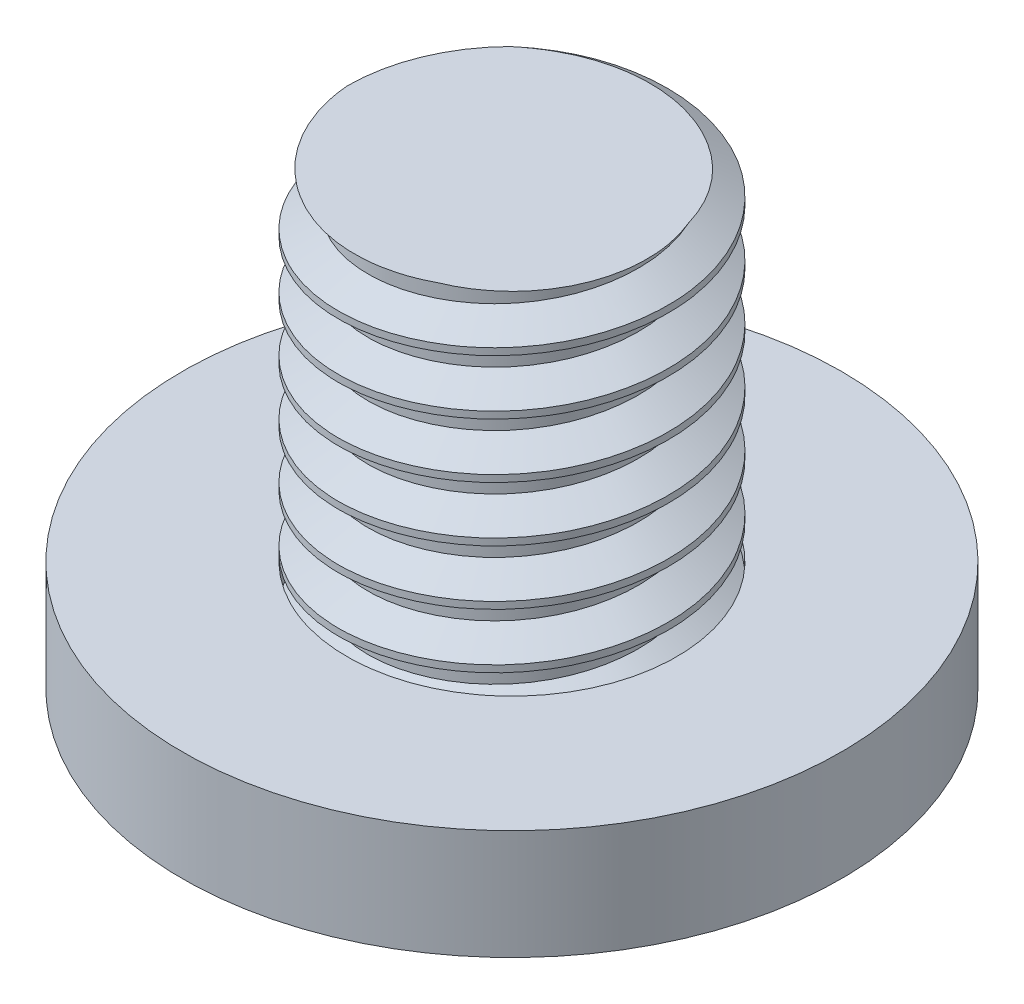
SolidWorks part; units mm, degrees
material "1060 合金"
ref_plane "前视基准面" through (0, 0, 0) normal (0, 0, 1) x (1, 0, 0)
ref_plane "上视基准面" through (0, 0, 0) normal (0, 1, 0) x (1, 0, 0)
ref_plane "右视基准面" through (0, 0, 0) normal (1, 0, 0) x (0, 0, -1)
sketch "草图1" plane through (0, 0, 0) normal (0, 0, 1) x (1, 0, 0)
  line L0 (0, -5.1495) -> (0, 3.6114) construction
  line L1 (-3, -2) -> (0, -2)
  line L2 (-3, -2) -> (-3, -1)
  line L3 (-3, -1) -> (-1.5, -1)
  line L4 (-1.5, -1) -> (-1.5, 2)
  line L5 (-1.5, 2) -> (0, 2)
  line L6 (0, 2) -> (0, -2)
  dimension "D1" = 3
  dimension "D2" = 3
  dimension "D3" = 1
  dimension "D4" = 6
revolve "旋转2" add sketch "草图1" angle 360 about L0
thread "螺纹线2" pitch 0.5 method cut profile "螺纹线轮廓2" start angle 0, offset 1, length 4, pitch 0.5, diameter 3
ref_plane "基准面2" through (-1.5, 3, 0) normal (0, 0, 1) x (-1, 0, 0)
sketch "螺纹线轮廓2" plane through (-1.5, 3, 0) normal (0, 0, 1) x (-1, 0, 0)
  line L0 (0, 0) -> (0, 0.5) construction
  line L11 (0, 0) -> (0, 0.4375)
  line L12 (0, 0.4375) -> (-0.2706, 0.2812)
  line L13 (-0.2706, 0.2812) -> (-0.2706, 0.1562)
  line L15 (-0.2706, 0.1562) -> (0, 0)
  line L17 (-0.2706, 0.2187) -> (0, 0.2187) construction
  point P2 (0, 0)
  dimension "Pitch" = 0.5
  dimension "Profile_Angle" = 60
  dimension "Profile_Land" = 0.125
  dimension "Profile_Height" = 0.2706
